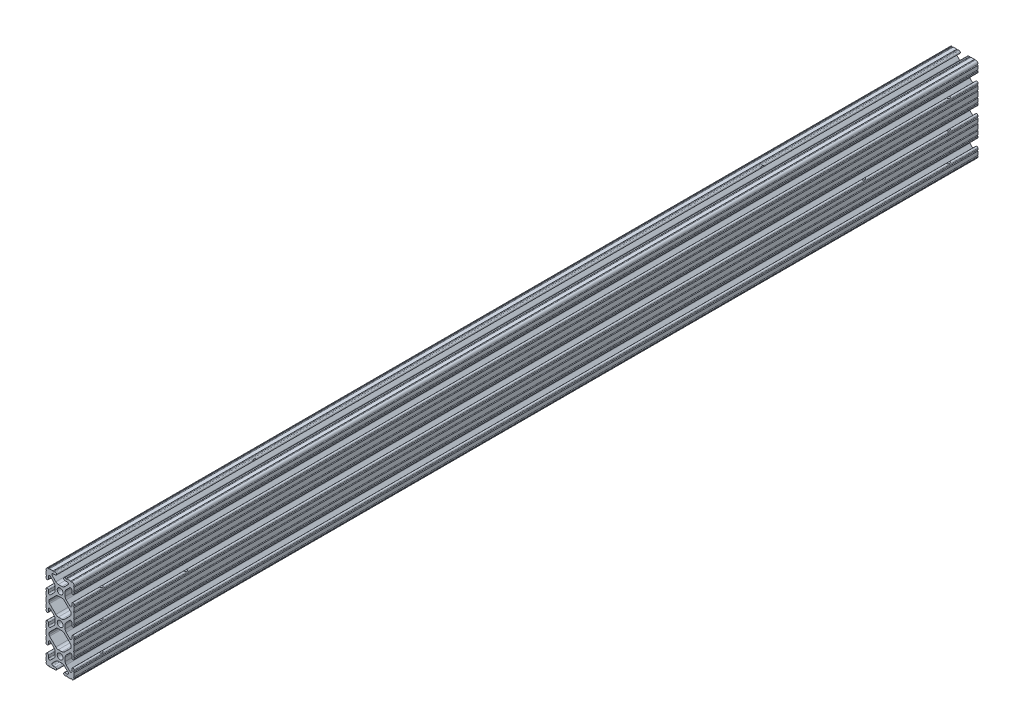
SolidWorks part; units mm, degrees
ref_plane "Front" through (0, 0, 0) normal (0, 0, 1) x (1, 0, 0)
ref_plane "Top" through (0, 0, 0) normal (0, 1, 0) x (1, 0, 0)
ref_plane "Right" through (0, 0, 0) normal (1, 0, 0) x (0, 0, -1)
sketch "Sketch1" plane through (0, 0, 0) normal (0, 0, 1) x (1, 0, 0)
  line L0 (-7.4908, -34.8742) -> (7.4908, -34.8742) construction
  line L1 (-3.1974, -36.9951) -> (3.1974, -36.9951) construction
  line L2 (-7.4908, 34.8742) -> (7.4908, 34.8742) construction
  line L3 (-3.1974, 36.9951) -> (3.1974, 36.9951) construction
  line L16 (-9.9314, -12.1463) -> (-9.9314, -13.2537)
  line L17 (-3.8759, -5.4384) -> (-9.4702, -11.0327)
  line L18 (1.6308, -4.5085) -> (-1.6308, -4.5085)
  line L19 (9.4702, -11.0327) -> (3.8759, -5.4384)
  line L20 (9.9314, -13.2537) -> (9.9314, -12.1463)
  line L21 (3.8759, -19.9616) -> (9.4702, -14.3673)
  line L22 (-1.6308, -20.8915) -> (1.6308, -20.8915)
  line L23 (-9.4702, -14.3673) -> (-3.8759, -19.9616)
  line L32 (-9.9314, 13.2537) -> (-9.9314, 12.1463)
  line L33 (-3.8759, 19.9616) -> (-9.4702, 14.3673)
  line L34 (1.6308, 20.8915) -> (-1.6308, 20.8915)
  line L35 (9.4702, 14.3673) -> (3.8759, 19.9616)
  line L36 (9.9314, 12.1463) -> (9.9314, 13.2537)
  line L37 (3.8759, 5.4384) -> (9.4702, 11.0327)
  line L38 (-1.6308, 4.5085) -> (1.6308, 4.5085)
  line L39 (-9.4702, 11.0327) -> (-3.8759, 5.4384)
  line L152 (-12.7, 34.9504) -> (-12.7, 31.7246)
  line L153 (-12.7, 30.7086) -> (-12.7, 29.7023)
  line L154 (-10.4902, 29.7023) -> (-10.4902, 31.8748)
  line L155 (-8.7558, 32.5932) -> (-5.4384, 29.2759)
  line L156 (-4.5085, 27.0308) -> (-4.5085, 23.7692)
  line L157 (-5.4384, 21.5241) -> (-8.7558, 18.2068)
  line L158 (-10.4902, 18.9252) -> (-10.4902, 21.0977)
  line L159 (-12.7, 21.0977) -> (-12.7, 20.0914)
  line L160 (-12.7, 19.0754) -> (-12.7, 15.8496)
  line L161 (-12.7, 14.8336) -> (-12.7, 10.5664)
  line L162 (-12.7, 9.5504) -> (-12.7, 6.3246)
  line L163 (-12.7, 5.3086) -> (-12.7, 4.3023)
  line L164 (-10.4902, 4.3023) -> (-10.4902, 6.4748)
  line L165 (-8.7558, 7.1932) -> (-5.4384, 3.8759)
  line L166 (-4.5085, 1.6308) -> (-4.5085, -1.6308)
  line L167 (-5.4384, -3.8759) -> (-8.7558, -7.1932)
  line L168 (-10.4902, -6.4748) -> (-10.4902, -4.3023)
  line L169 (-12.7, -4.3023) -> (-12.7, -5.3086)
  line L170 (-12.7, -6.3246) -> (-12.7, -9.5504)
  line L171 (-12.7, -10.5664) -> (-12.7, -14.8336)
  line L172 (-12.7, -15.8496) -> (-12.7, -19.0754)
  line L173 (-12.7, -20.0914) -> (-12.7, -21.0977)
  line L174 (-10.4902, -21.0977) -> (-10.4902, -18.9252)
  line L175 (-8.7558, -18.2068) -> (-5.4384, -21.5241)
  line L176 (-4.5085, -23.7692) -> (-4.5085, -27.0308)
  line L177 (-5.4384, -29.2759) -> (-8.7558, -32.5932)
  line L178 (-10.4902, -31.8748) -> (-10.4902, -29.7023)
  line L179 (-12.7, -29.7023) -> (-12.7, -30.7086)
  line L180 (-12.7, -31.7246) -> (-12.7, -34.9504)
  line L181 (-9.5504, -38.1) -> (-6.3246, -38.1)
  line L182 (-5.3086, -38.1) -> (-4.3023, -38.1)
  line L183 (-4.3023, -35.8902) -> (-6.4748, -35.8902)
  line L184 (-7.1932, -34.1558) -> (-3.8759, -30.8384)
  line L185 (-1.6308, -29.9085) -> (1.6308, -29.9085)
  line L186 (3.8759, -30.8384) -> (7.1932, -34.1558)
  line L187 (6.4748, -35.8902) -> (4.3023, -35.8902)
  line L188 (4.3023, -38.1) -> (5.3086, -38.1)
  line L189 (6.3246, -38.1) -> (9.5504, -38.1)
  line L190 (12.7, -34.9504) -> (12.7, -31.7246)
  line L191 (12.7, -30.7086) -> (12.7, -29.7023)
  line L192 (10.4902, -29.7023) -> (10.4902, -31.8748)
  line L193 (8.7558, -32.5932) -> (5.4384, -29.2759)
  line L194 (4.5085, -27.0308) -> (4.5085, -23.7692)
  line L195 (5.4384, -21.5241) -> (8.7558, -18.2068)
  line L196 (10.4902, -18.9252) -> (10.4902, -21.0977)
  line L197 (12.7, -21.0977) -> (12.7, -20.0914)
  line L198 (12.7, -19.0754) -> (12.7, -15.8496)
  line L199 (12.7, -14.8336) -> (12.7, -10.5664)
  line L200 (12.7, -9.5504) -> (12.7, -6.3246)
  line L201 (12.7, -5.3086) -> (12.7, -4.3023)
  line L202 (10.4902, -4.3023) -> (10.4902, -6.4748)
  line L203 (8.7558, -7.1932) -> (5.4384, -3.8759)
  line L204 (4.5085, -1.6308) -> (4.5085, 1.6308)
  line L205 (5.4384, 3.8759) -> (8.7558, 7.1932)
  line L206 (10.4902, 6.4748) -> (10.4902, 4.3023)
  line L207 (12.7, 4.3023) -> (12.7, 5.3086)
  line L208 (12.7, 6.3246) -> (12.7, 9.5504)
  line L209 (12.7, 10.5664) -> (12.7, 14.8336)
  line L210 (12.7, 15.8496) -> (12.7, 19.0754)
  line L211 (12.7, 20.0914) -> (12.7, 21.0977)
  line L212 (10.4902, 21.0977) -> (10.4902, 18.9252)
  line L213 (8.7558, 18.2068) -> (5.4384, 21.5241)
  line L214 (4.5085, 23.7692) -> (4.5085, 27.0308)
  line L215 (5.4384, 29.2759) -> (8.7558, 32.5932)
  line L216 (10.4902, 31.8748) -> (10.4902, 29.7023)
  line L217 (12.7, 29.7023) -> (12.7, 30.7086)
  line L218 (12.7, 31.7246) -> (12.7, 34.9504)
  line L219 (9.5504, 38.1) -> (6.3246, 38.1)
  line L220 (5.3086, 38.1) -> (4.3023, 38.1)
  line L221 (4.3023, 35.8902) -> (6.4748, 35.8902)
  line L222 (7.1932, 34.1558) -> (3.8759, 30.8384)
  line L223 (1.6308, 29.9085) -> (-1.6308, 29.9085)
  line L224 (-3.8759, 30.8384) -> (-7.1932, 34.1558)
  line L225 (-6.4748, 35.8902) -> (-4.3023, 35.8902)
  line L226 (-4.3023, 38.1) -> (-5.3086, 38.1)
  line L227 (-6.3246, 38.1) -> (-9.5504, 38.1)
  circle A2 centre (0, -25.4) radius 2.6035
  circle A4 centre (0, 0) radius 2.6035
  circle A6 centre (0, 25.4) radius 2.6035
  arc A18 (-9.9314, -13.2537) -> (-9.4702, -14.3673) centre (-8.3566, -13.2537) ccw
  arc A19 (-9.4702, -11.0327) -> (-9.9314, -12.1463) centre (-8.3566, -12.1463) ccw
  arc A20 (-1.6308, -4.5085) -> (-3.8759, -5.4384) centre (-1.6308, -7.6835) ccw
  arc A21 (3.8759, -5.4384) -> (1.6308, -4.5085) centre (1.6308, -7.6835) ccw
  arc A22 (9.9314, -12.1463) -> (9.4702, -11.0327) centre (8.3566, -12.1463) ccw
  arc A23 (9.4702, -14.3673) -> (9.9314, -13.2537) centre (8.3566, -13.2537) ccw
  arc A24 (1.6308, -20.8915) -> (3.8759, -19.9616) centre (1.6308, -17.7165) ccw
  arc A25 (-3.8759, -19.9616) -> (-1.6308, -20.8915) centre (-1.6308, -17.7165) ccw
  arc A36 (-9.9314, 12.1463) -> (-9.4702, 11.0327) centre (-8.3566, 12.1463) ccw
  arc A37 (-9.4702, 14.3673) -> (-9.9314, 13.2537) centre (-8.3566, 13.2537) ccw
  arc A38 (-1.6308, 20.8915) -> (-3.8759, 19.9616) centre (-1.6308, 17.7165) ccw
  arc A39 (3.8759, 19.9616) -> (1.6308, 20.8915) centre (1.6308, 17.7165) ccw
  arc A40 (9.9314, 13.2537) -> (9.4702, 14.3673) centre (8.3566, 13.2537) ccw
  arc A41 (9.4702, 11.0327) -> (9.9314, 12.1463) centre (8.3566, 12.1463) ccw
  arc A42 (1.6308, 4.5085) -> (3.8759, 5.4384) centre (1.6308, 7.6835) ccw
  arc A43 (-3.8759, 5.4384) -> (-1.6308, 4.5085) centre (-1.6308, 7.6835) ccw
  arc A168 (-10.5664, 38.1) -> (-12.7, 35.9664) centre (-10.592, 35.992) ccw
  arc A169 (-12.7, 34.9504) -> (-12.7, 35.9664) centre (-12.7, 35.4584) ccw
  arc A170 (-12.7, 30.7086) -> (-12.7, 31.7246) centre (-12.7, 31.2166) ccw
  arc A171 (-12.7, 29.7023) -> (-10.4902, 29.7023) centre (-11.5951, 29.7023) ccw
  arc A172 (-8.7558, 32.5932) -> (-10.4902, 31.8748) centre (-9.4742, 31.8748) ccw
  arc A173 (-4.5085, 27.0308) -> (-5.4384, 29.2759) centre (-7.6835, 27.0308) ccw
  arc A174 (-5.4384, 21.5241) -> (-4.5085, 23.7692) centre (-7.6835, 23.7692) ccw
  arc A175 (-10.4902, 18.9252) -> (-8.7558, 18.2068) centre (-9.4742, 18.9252) ccw
  arc A176 (-10.4902, 21.0977) -> (-12.7, 21.0977) centre (-11.5951, 21.0977) ccw
  arc A177 (-12.7, 19.0754) -> (-12.7, 20.0914) centre (-12.7, 19.5834) ccw
  arc A178 (-12.7, 14.8336) -> (-12.7, 15.8496) centre (-12.7, 15.3416) ccw
  arc A179 (-12.7, 9.5504) -> (-12.7, 10.5664) centre (-12.7, 10.0584) ccw
  arc A180 (-12.7, 5.3086) -> (-12.7, 6.3246) centre (-12.7, 5.8166) ccw
  arc A181 (-12.7, 4.3023) -> (-10.4902, 4.3023) centre (-11.5951, 4.3023) ccw
  arc A182 (-8.7558, 7.1932) -> (-10.4902, 6.4748) centre (-9.4742, 6.4748) ccw
  arc A183 (-4.5085, 1.6308) -> (-5.4384, 3.8759) centre (-7.6835, 1.6308) ccw
  arc A184 (-5.4384, -3.8759) -> (-4.5085, -1.6308) centre (-7.6835, -1.6308) ccw
  arc A185 (-10.4902, -6.4748) -> (-8.7558, -7.1932) centre (-9.4742, -6.4748) ccw
  arc A186 (-10.4902, -4.3023) -> (-12.7, -4.3023) centre (-11.5951, -4.3023) ccw
  arc A187 (-12.7, -6.3246) -> (-12.7, -5.3086) centre (-12.7, -5.8166) ccw
  arc A188 (-12.7, -10.5664) -> (-12.7, -9.5504) centre (-12.7, -10.0584) ccw
  arc A189 (-12.7, -15.8496) -> (-12.7, -14.8336) centre (-12.7, -15.3416) ccw
  arc A190 (-12.7, -20.0914) -> (-12.7, -19.0754) centre (-12.7, -19.5834) ccw
  arc A191 (-12.7, -21.0977) -> (-10.4902, -21.0977) centre (-11.5951, -21.0977) ccw
  arc A192 (-8.7558, -18.2068) -> (-10.4902, -18.9252) centre (-9.4742, -18.9252) ccw
  arc A193 (-4.5085, -23.7692) -> (-5.4384, -21.5241) centre (-7.6835, -23.7692) ccw
  arc A194 (-5.4384, -29.2759) -> (-4.5085, -27.0308) centre (-7.6835, -27.0308) ccw
  arc A195 (-10.4902, -31.8748) -> (-8.7558, -32.5932) centre (-9.4742, -31.8748) ccw
  arc A196 (-10.4902, -29.7023) -> (-12.7, -29.7023) centre (-11.5951, -29.7023) ccw
  arc A197 (-12.7, -31.7246) -> (-12.7, -30.7086) centre (-12.7, -31.2166) ccw
  arc A198 (-12.7, -35.9664) -> (-12.7, -34.9504) centre (-12.7, -35.4584) ccw
  arc A199 (-12.7, -35.9664) -> (-10.5664, -38.1) centre (-10.592, -35.992) ccw
  arc A200 (-9.5504, -38.1) -> (-10.5664, -38.1) centre (-10.0584, -38.1) ccw
  arc A201 (-5.3086, -38.1) -> (-6.3246, -38.1) centre (-5.8166, -38.1) ccw
  arc A202 (-4.3023, -38.1) -> (-4.3023, -35.8902) centre (-4.3023, -36.9951) ccw
  arc A203 (-7.1932, -34.1558) -> (-6.4748, -35.8902) centre (-6.4748, -34.8742) ccw
  arc A204 (-1.6308, -29.9085) -> (-3.8759, -30.8384) centre (-1.6308, -33.0835) ccw
  arc A205 (3.8759, -30.8384) -> (1.6308, -29.9085) centre (1.6308, -33.0835) ccw
  arc A206 (6.4748, -35.8902) -> (7.1932, -34.1558) centre (6.4748, -34.8742) ccw
  arc A207 (4.3023, -35.8902) -> (4.3023, -38.1) centre (4.3023, -36.9951) ccw
  arc A208 (6.3246, -38.1) -> (5.3086, -38.1) centre (5.8166, -38.1) ccw
  arc A209 (10.5664, -38.1) -> (9.5504, -38.1) centre (10.0584, -38.1) ccw
  arc A210 (10.5664, -38.1) -> (12.7, -35.9664) centre (10.592, -35.992) ccw
  arc A211 (12.7, -34.9504) -> (12.7, -35.9664) centre (12.7, -35.4584) ccw
  arc A212 (12.7, -30.7086) -> (12.7, -31.7246) centre (12.7, -31.2166) ccw
  arc A213 (12.7, -29.7023) -> (10.4902, -29.7023) centre (11.5951, -29.7023) ccw
  arc A214 (8.7558, -32.5932) -> (10.4902, -31.8748) centre (9.4742, -31.8748) ccw
  arc A215 (4.5085, -27.0308) -> (5.4384, -29.2759) centre (7.6835, -27.0308) ccw
  arc A216 (5.4384, -21.5241) -> (4.5085, -23.7692) centre (7.6835, -23.7692) ccw
  arc A217 (10.4902, -18.9252) -> (8.7558, -18.2068) centre (9.4742, -18.9252) ccw
  arc A218 (10.4902, -21.0977) -> (12.7, -21.0977) centre (11.5951, -21.0977) ccw
  arc A219 (12.7, -19.0754) -> (12.7, -20.0914) centre (12.7, -19.5834) ccw
  arc A220 (12.7, -14.8336) -> (12.7, -15.8496) centre (12.7, -15.3416) ccw
  arc A221 (12.7, -9.5504) -> (12.7, -10.5664) centre (12.7, -10.0584) ccw
  arc A222 (12.7, -5.3086) -> (12.7, -6.3246) centre (12.7, -5.8166) ccw
  arc A223 (12.7, -4.3023) -> (10.4902, -4.3023) centre (11.5951, -4.3023) ccw
  arc A224 (8.7558, -7.1932) -> (10.4902, -6.4748) centre (9.4742, -6.4748) ccw
  arc A225 (4.5085, -1.6308) -> (5.4384, -3.8759) centre (7.6835, -1.6308) ccw
  arc A226 (5.4384, 3.8759) -> (4.5085, 1.6308) centre (7.6835, 1.6308) ccw
  arc A227 (10.4902, 6.4748) -> (8.7558, 7.1932) centre (9.4742, 6.4748) ccw
  arc A228 (10.4902, 4.3023) -> (12.7, 4.3023) centre (11.5951, 4.3023) ccw
  arc A229 (12.7, 6.3246) -> (12.7, 5.3086) centre (12.7, 5.8166) ccw
  arc A230 (12.7, 10.5664) -> (12.7, 9.5504) centre (12.7, 10.0584) ccw
  arc A231 (12.7, 15.8496) -> (12.7, 14.8336) centre (12.7, 15.3416) ccw
  arc A232 (12.7, 20.0914) -> (12.7, 19.0754) centre (12.7, 19.5834) ccw
  arc A233 (12.7, 21.0977) -> (10.4902, 21.0977) centre (11.5951, 21.0977) ccw
  arc A234 (8.7558, 18.2068) -> (10.4902, 18.9252) centre (9.4742, 18.9252) ccw
  arc A235 (4.5085, 23.7692) -> (5.4384, 21.5241) centre (7.6835, 23.7692) ccw
  arc A236 (5.4384, 29.2759) -> (4.5085, 27.0308) centre (7.6835, 27.0308) ccw
  arc A237 (10.4902, 31.8748) -> (8.7558, 32.5932) centre (9.4742, 31.8748) ccw
  arc A238 (10.4902, 29.7023) -> (12.7, 29.7023) centre (11.5951, 29.7023) ccw
  arc A239 (12.7, 31.7246) -> (12.7, 30.7086) centre (12.7, 31.2166) ccw
  arc A240 (12.7, 35.9664) -> (12.7, 34.9504) centre (12.7, 35.4584) ccw
  arc A241 (12.7, 35.9664) -> (10.5664, 38.1) centre (10.592, 35.992) ccw
  arc A242 (9.5504, 38.1) -> (10.5664, 38.1) centre (10.0584, 38.1) ccw
  arc A243 (5.3086, 38.1) -> (6.3246, 38.1) centre (5.8166, 38.1) ccw
  arc A244 (4.3023, 38.1) -> (4.3023, 35.8902) centre (4.3023, 36.9951) ccw
  arc A245 (7.1932, 34.1558) -> (6.4748, 35.8902) centre (6.4748, 34.8742) ccw
  arc A246 (1.6308, 29.9085) -> (3.8759, 30.8384) centre (1.6308, 33.0835) ccw
  arc A247 (-3.8759, 30.8384) -> (-1.6308, 29.9085) centre (-1.6308, 33.0835) ccw
  arc A248 (-6.4748, 35.8902) -> (-7.1932, 34.1558) centre (-6.4748, 34.8742) ccw
  arc A249 (-4.3023, 35.8902) -> (-4.3023, 38.1) centre (-4.3023, 36.9951) ccw
  arc A250 (-6.3246, 38.1) -> (-5.3086, 38.1) centre (-5.8166, 38.1) ccw
  arc A251 (-10.5664, 38.1) -> (-9.5504, 38.1) centre (-10.0584, 38.1) ccw
extrude "Boss-Extrude1" add sketch "Sketch1" along normal mid plane 812.8
sketch "Sketch2" plane through (4.5085, 0, 0) normal (1, 0, 0) x (0, 0, -1)
  line L0 (-406.4, 38.1) -> (406.4, 38.1) construction
  line L1 (-406.4, 23.7692) -> (-406.4, 27.0308) construction
  line L2 (-406.4, -1.6308) -> (-406.4, 1.6308) construction
  line L3 (-406.4, -27.0308) -> (-406.4, -23.7692) construction
  line L4 (0, 0) -> (0, 56.395) construction
  circle A0 centre (-381, 25.4) radius 3.5
  circle A1 centre (-381, 0) radius 3.5
  circle A2 centre (-381, -25.4) radius 3.5
  circle A3 centre (381, 25.4) radius 3.5
  circle A4 centre (381, 0) radius 3.5
  circle A5 centre (381, -25.4) radius 3.5
  dimension "D1" = 7
  dimension "D2" = 12.7
  dimension "D3" = 25.4
  dimension "D4" = 7
  dimension "D5" = 7
  dimension "D6" = 25.4
  dimension "D7" = 25.4
  dimension "D8" = 25.4
  dimension "D9" = 25.4
extrude "Cut-Extrude1" cut sketch "Sketch2" against normal through all both and the other way through all
sketch "Sketch3" plane through (4.5085, 0, 0) normal (1, 0, 0) x (0, 0, -1)
  line L0 (0, 0) -> (0, 69.8838) construction
  line L1 (-406.4, -1.6308) -> (-406.4, 1.6308) construction
  line L2 (-406.4, 38.1) -> (406.4, 38.1) construction
  circle A0 centre (-304.8, 0) radius 3.5
  circle A1 centre (304.8, 0) radius 3.5
  dimension "D1" = 7
  dimension "D2" = 101.6
  dimension "D3" = 38.1
extrude "Cut-Extrude2" cut sketch "Sketch3" against normal through all both and the other way through all
sketch "Sketch4" plane through (0, -29.9085, 0) normal (0, -1, 0) x (1, 0, 0)
  line L0 (0, 0) -> (131.3157, 0) construction
  line L1 (-1.6308, 406.4) -> (1.6308, 406.4) construction
  circle A0 centre (0, 228.53) radius 3.5
  circle A1 centre (0, -228.53) radius 3.5
  dimension "D1" = 7
  dimension "D2" = 177.87
extrude "Cut-Extrude3" cut sketch "Sketch4" against normal through all both and the other way through all
